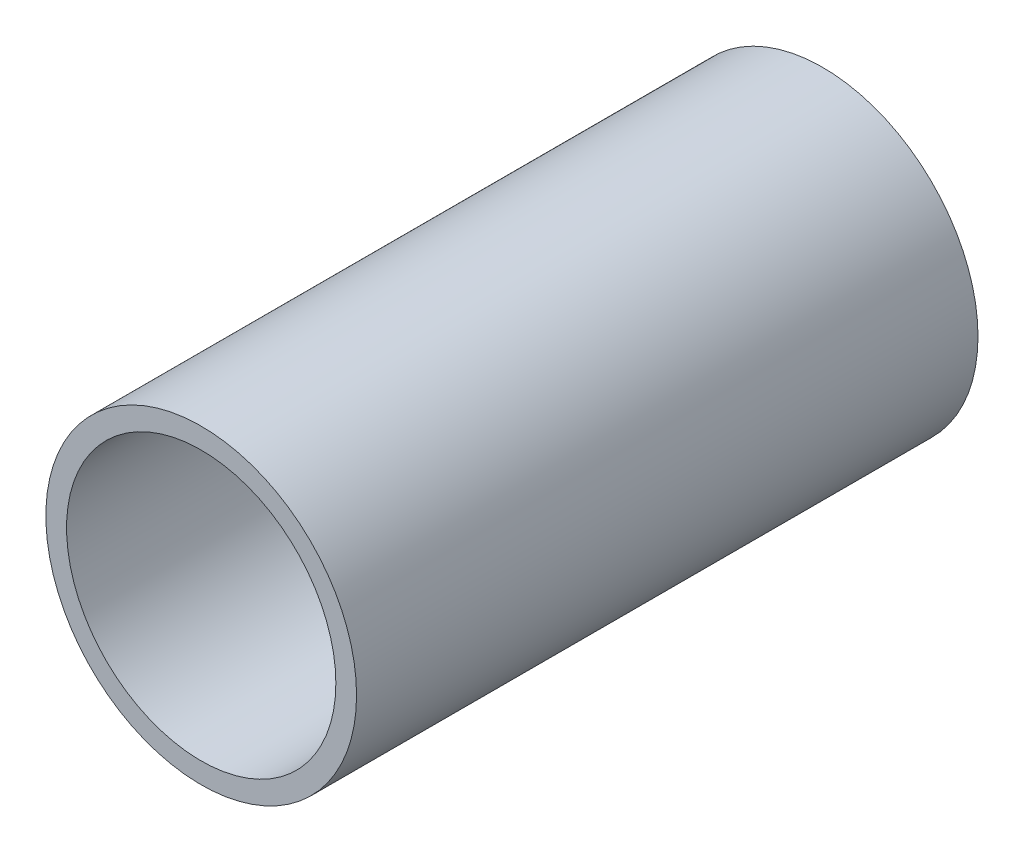
SolidWorks part; units mm, degrees
ref_plane "Front" through (0, 0, 0) normal (0, 0, 1) x (1, 0, 0)
ref_plane "Top" through (0, 0, 0) normal (0, 1, 0) x (1, 0, 0)
ref_plane "Right" through (0, 0, 0) normal (1, 0, 0) x (0, 0, -1)
sketch "Sketch1" plane through (0, 0, 0) normal (0, 0, 1) x (1, 0, 0)
  circle A0 centre (0, 0) radius 7.5
  circle A1 centre (0, 0) radius 6.5
  dimension "D1" = 1
  dimension "D2" = 13
extrude "Boss-Extrude1" add sketch "Sketch1" along normal blind 30
ref_point "Point1"
ref_point "Point2"
ref_axis "Axis1" through (0, 0, 30) along (0, 1, 0)
ref_axis "Axis2" through (0, 0, 0) along (0, 1, 0)
